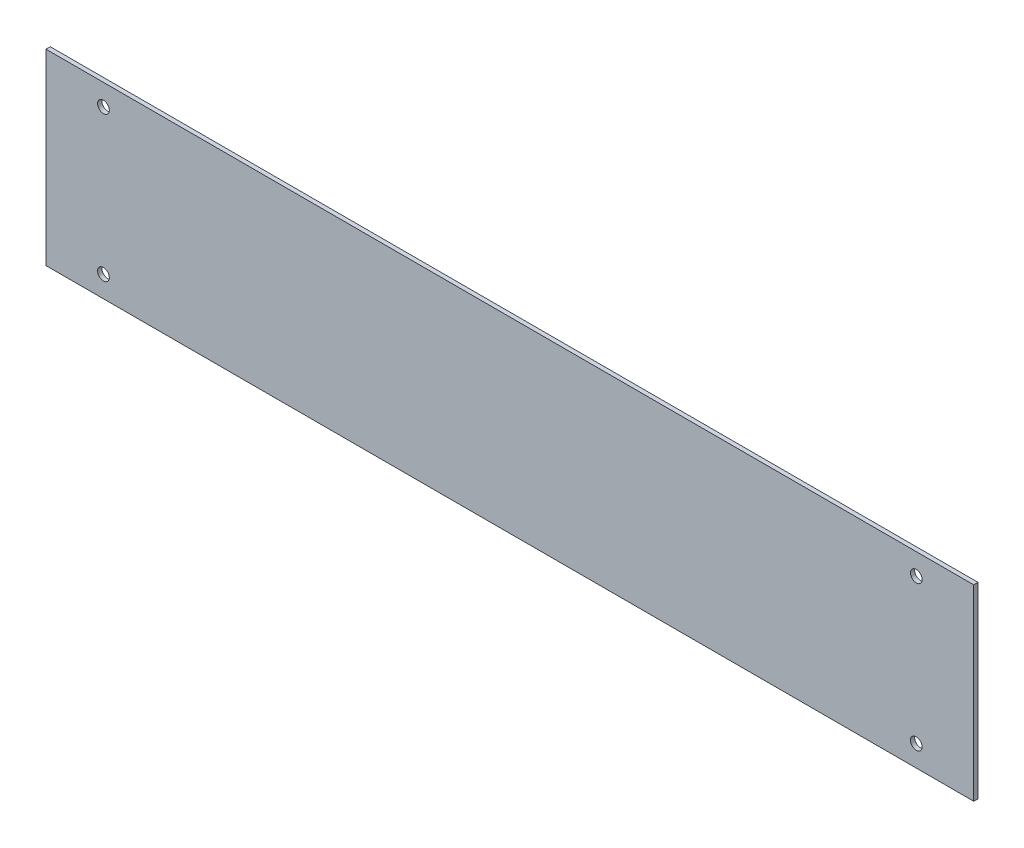
SolidWorks part; units mm, degrees
material "1060 Сплав"
ref_plane "Front" through (0, 0, 0) normal (0, 0, 1) x (1, 0, 0)
ref_plane "Top" through (0, 0, 0) normal (0, 1, 0) x (1, 0, 0)
ref_plane "Right" through (0, 0, 0) normal (1, 0, 0) x (0, 0, -1)
sketch "Эскиз1" plane through (0, 0, 0) normal (0, 0, 1) x (1, 0, 0)
  line L1 (0, 0) -> (436, 0)
  line L2 (0, 0) -> (0, 88.1)
  line L3 (0, 88.1) -> (436, 88.1)
  line L4 (436, 0) -> (436, 88.1)
  point P9 (436, 88.1)
  point P12 (0, 0)
  point P15 (0, 88.1)
  dimension "D1" = 88.1
  dimension "D2" = 436
extrude "Бобышка-Вытянуть1" add sketch "Эскиз1" along normal blind 2
sketch "Эскиз6" plane through (0, 0, 0) normal (0, 0, -1) x (-1, 0, 0)
  line L0 (-436, 88.1) -> (0, 88.1) construction
  line L1 (-436, 0) -> (-436, 88.1) construction
  circle A0 centre (-409, 78.1) radius 2.75
  circle A1 centre (-409, 10) radius 2.75
  circle A2 centre (-27, 10) radius 2.75
  circle A3 centre (-27, 78.1) radius 2.75
  dimension "D1" = 5.5
  dimension "D2" = 5.5
  dimension "D3" = 5.5
  dimension "D4" = 5.5
  dimension "D5" = 68.1
  dimension "D6" = 10
  dimension "D7" = 27
  dimension "D8" = 27
  dimension "D9" = 382
  dimension "D10" = 10
  dimension "D11" = 68.1
  dimension "D12" = 382
extrude "Вырез-Вытянуть1" cut sketch "Эскиз6" against normal through all
